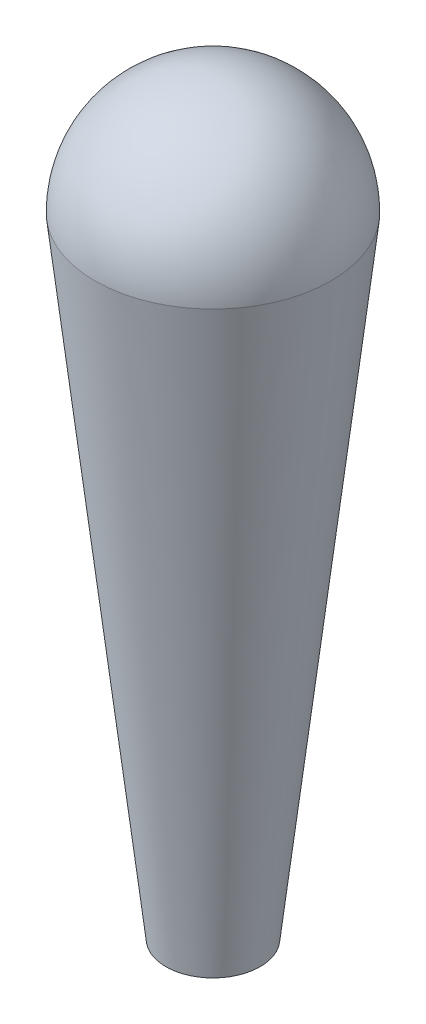
SolidWorks part; units mm, degrees
ref_plane "Front Plane" through (0, 0, 0) normal (0, 0, 1) x (1, 0, 0)
ref_plane "Top Plane" through (0, 0, 0) normal (0, 1, 0) x (1, 0, 0)
ref_plane "Right Plane" through (0, 0, 0) normal (1, 0, 0) x (0, 0, -1)
sketch "Sketch1" plane through (0, 0, 0) normal (0, 0, 1) x (1, 0, 0)
  line L0 (0, 0) -> (0, 101.6)
  line L1 (0, -55) -> (0, 55) construction
  line L2 (0, 101.6) -> (19.05, 101.6)
  line L3 (19.05, 101.6) -> (7.62, 0)
  line L4 (55, 0) -> (-55, 0) construction
  line L5 (7.62, 0) -> (0, 0)
  dimension "D1" = 101.6
  dimension "D2" = 19.05
  dimension "D3" = 7.62
revolve "Revolve1" add sketch "Sketch1" angle 360 about L0
dome "Dome1" faces to dome 1 distance 19.05 reverse direction no elliptical dome no face at (0, 101.6, -19.05) parameters "D1"=19.05
